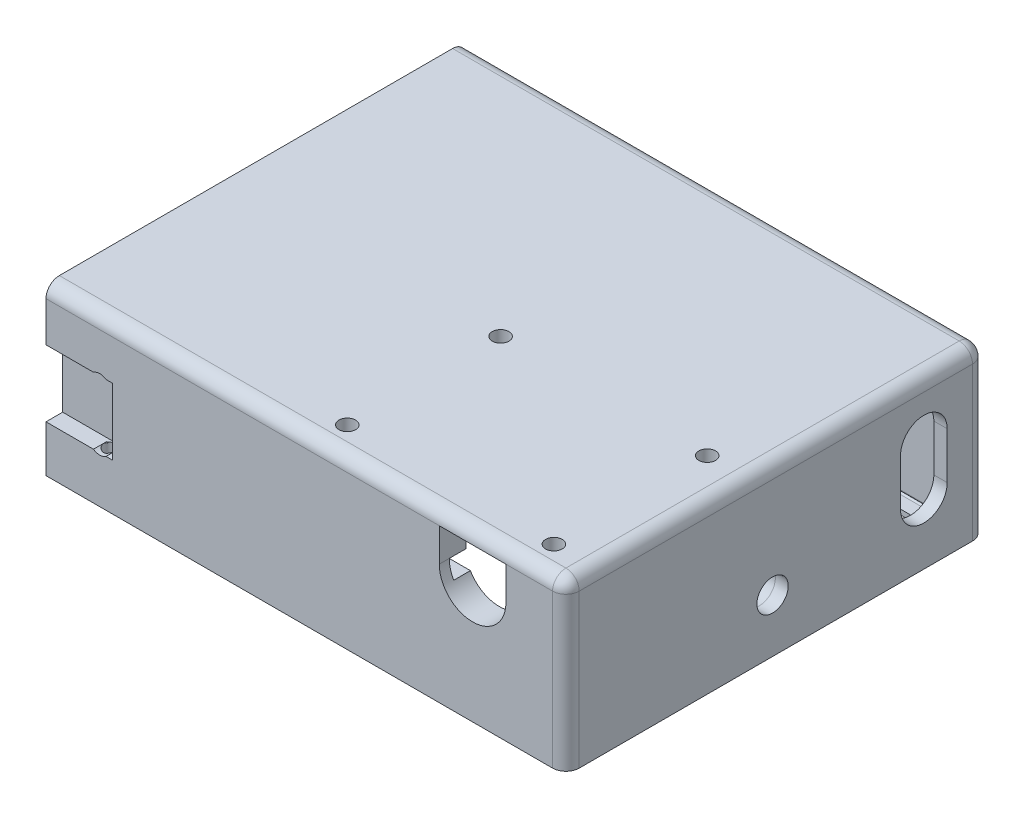
SolidWorks part; units mm, degrees
note: The reader was unsure of these and kept them because the rebuilt part matched: shared geometry of "Sketch1<4>", "Sketch18<3>".
ref_plane "Front Plane" through (0, 0, 0) normal (0, 0, 1) x (1, 0, 0)
ref_plane "Top Plane" through (0, 0, 0) normal (0, 1, 0) x (1, 0, 0)
ref_plane "Right Plane" through (0, 0, 0) normal (1, 0, 0) x (0, 0, -1)
sketch "Sketch1" plane through (0, 0, 0) normal (0, 1, 0) x (1, 0, 0)
  line L1 (0, 0) -> (80, 0)
  line L2 (0, 0) -> (0, 63)
  line L3 (0, 63) -> (80, 63)
  line L4 (80, 0) -> (80, 63)
  line L5 (2, 4) -> (78, 4)
  line L6 (2, 4) -> (2, 59)
  line L7 (2, 59) -> (78, 59)
  line L8 (78, 4) -> (78, 59)
  line L9 (0, 0) -> (2, 0)
  line L10 (0, 0) -> (0, 63)
  line L11 (0, 63) -> (2, 63)
  line L12 (2, 0) -> (2, 63)
  dimension "D1" = 63
  dimension "Length" = 80
  dimension "D2" = 2
  dimension "D3" = 4
  dimension "D4" = 2
  dimension "D5" = 4
extrude "Boss-Extrude2" add sketch "Sketch1" along normal blind 25 contours L1 L4 L3 L2
extrude "Cut-Extrude1" cut sketch "Sketch1<4>" along normal blind 23 contours L5 L8 L7 L6
sketch "Sketch1<4>" plane through (0, 0, 0) normal (0, 1, 0) x (1, 0, 0) same geometry as "Sketch1"
sketch "Sketch3" plane through (80, 0, 0) normal (1, 0, 0) x (0, 0, -1)
  line L0 (46.5, 10) -> (16.5, 10) construction
  line L1 (46.5, 7.5) -> (16.5, 7.5)
  line L2 (46.5, 12.5) -> (16.5, 12.5)
  line L3 (4, 0) -> (59, 0) construction
  line L4 (0, 25) -> (0, 0) construction
  arc A0 (46.5, 7.5) -> (46.5, 12.5) centre (46.5, 10) ccw
  arc A1 (16.5, 12.5) -> (16.5, 7.5) centre (16.5, 10) ccw
  point P2 (31.5, 10)
  dimension "D1" = 30
  dimension "D2" = 5
  dimension "D3" = 10
  dimension "D4" = 31.5
sketch "Sketch4" plane through (0, 23, 0) normal (0, -1, 0) x (1, 0, 0)
  line L0 (2, -4) -> (78, -4) construction
  line L1 (29.5, -4) -> (31.5, -4)
  line L2 (29.5, -4) -> (29.5, -59)
  line L3 (29.5, -59) -> (31.5, -59)
  line L4 (31.5, -4) -> (31.5, -59)
  line L5 (2, -59) -> (78, -59) construction
  line L6 (2, -4) -> (2, -59) construction
  dimension "D1" = 2
  dimension "D2" = 27.5
extrude "Boss-Extrude3" add sketch "Sketch4" along normal blind 10
fillet "Fillet1" radius 2 8 edges at (40, 25, -63) (0, 12.5, -63) (0, 25, -31.5) (0, 12.5, 0) (40, 25, 0) (80, 12.5, 0) (80, 25, -31.5) (80, 12.5, -63)
sketch "Sketch5" plane through (0, 0, 0) normal (0, -1, 0) x (-1, 0, 0)
  line L1 (0, 0) -> (-2, 0)
  line L2 (0, 0) -> (0, 63)
  line L3 (0, 63) -> (-2, 63)
  line L4 (-2, 0) -> (-2, 63)
extrude "Cut-Extrude3" cut sketch "Sketch5" against normal through all
sketch "Sketch6" plane through (2, 0, 0) normal (-1, 0, 0) x (0, 0, 1)
  line L0 (-4, 23) -> (-4, 0) construction
  line L1 (-4, 0.75) -> (-1.8, 0.75)
  line L2 (-4, 0.75) -> (-4, 2.95)
  line L3 (-4, 2.95) -> (-1.8, 2.95)
  line L4 (-1.8, 0.75) -> (-1.8, 2.95)
  line L5 (-59, 23) -> (-59, 0) construction
  line L6 (-59, 0.75) -> (-61.2, 0.75)
  line L7 (-59, 0.75) -> (-59, 2.95)
  line L8 (-59, 2.95) -> (-61.2, 2.95)
  line L9 (-61.2, 0.75) -> (-61.2, 2.95)
  line L10 (0, 0) -> (-63, 0) construction
  line L11 (0, 23) -> (0, 0) construction
  point P12 (-60.1, 2.95)
  point P17 (-1.8, 1.85)
  dimension "D1" = 2.2
  dimension "D2" = 2.2
  dimension "D3" = 2.2
  dimension "D4" = 0.75
  dimension "D5" = 0.75
  dimension "1.5" = 2.2
  dimension "D6" = 1.8
extrude "Cut-Extrude4" cut sketch "Sketch6" against normal blind 76 contours L6 L9 L8 L7 | L1 L4 L3 L2
sketch "Sketch7" plane through (0, 0, -63) normal (0, 0, -1) x (-1, 0, 0)
  line L0 (-2, 0) -> (-2, 23) construction
  line L1 (-2, 7) -> (-12, 7)
  line L2 (-2, 7) -> (-2, 17)
  line L3 (-2, 17) -> (-12, 17)
  line L4 (-12, 7) -> (-12, 17)
  line L5 (-78, 25) -> (-2, 25) construction
  dimension "D1" = 10
  dimension "D2" = 8
  dimension "D3" = 10
extrude "Cut-Extrude5" cut sketch "Sketch7" against normal blind 2.5
sketch "Sketch8" plane through (0, 7, 0) normal (0, 1, 0) x (1, 0, 0)
  line L0 (12, 60.5) -> (12, 63) construction
  line L1 (12, 60.5) -> (2, 60.5) construction
  circle A0 centre (10, 61.5) radius 0.875
  dimension "D1" = 1.75
  dimension "D2" = 2
  dimension "D3" = 1
extrude "Cut-Extrude6" cut sketch "Sketch8" against normal blind 1.5 and the other way blind 11.5
sketch "Sketch9" plane through (0, 0, 0) normal (0, 0, 1) x (1, 0, 0)
  line L0 (2, 23) -> (2, 0) construction
  line L1 (2, 7) -> (12, 7)
  line L2 (2, 7) -> (2, 17)
  line L3 (2, 17) -> (12, 17)
  line L4 (12, 7) -> (12, 17)
  line L5 (2, 25) -> (78, 25) construction
  dimension "D1" = 10
  dimension "D2" = 10
  dimension "D3" = 8
extrude "Cut-Extrude7" cut sketch "Sketch9" against normal blind 2.5
sketch "Sketch10" plane through (0, 7, 0) normal (0, 1, 0) x (1, 0, 0)
  line L0 (12, 2.5) -> (12, 0) construction
  line L1 (2, 2.5) -> (12, 2.5) construction
  circle A0 centre (10, 1.5) radius 0.875
  dimension "D1" = 1.75
  dimension "D2" = 2
  dimension "D3" = 1
extrude "Cut-Extrude8" cut sketch "Sketch10" against normal blind 1.5 and the other way blind 11.5
sketch "Sketch11" plane through (0, 0, -63) normal (0, 0, -1) x (-1, 0, 0)
  line L0 (-12, 7) -> (-2, 7) construction
  line L1 (-9.123, 7) -> (-10.8, 7)
  line L2 (-12, 12) -> (-17.0656, 12) construction
  line L3 (-12, 17) -> (-12, 7) construction
  line L4 (-9.123, 17) -> (-10.8, 17)
  spline S0 degree 2 poles (-10.8, 7) (-9.9802, 6.3956) (-9.123, 7) knots 0 0 0 1 1 1
  spline S1 degree 2 poles (-10.8, 17) (-9.9802, 17.6044) (-9.123, 17) knots 0 0 0 1 1 1
  dimension "D1" = 0.3
  dimension "D2" = 1.2
extrude "Cut-Extrude9" cut sketch "Sketch11" against normal blind 2 contours S0 L1 | S1 L4
sketch "Sketch12" plane through (0, 0, 0) normal (0, 0, 1) x (1, 0, 0)
  line L0 (2, 7) -> (12, 7) construction
  line L2 (11, 7) -> (9.1201, 7)
  line L3 (12, 12) -> (18.6065, 12) construction
  line L4 (12, 7) -> (12, 17) construction
  line L5 (11, 17) -> (9.1201, 17)
  spline S0 degree 2 poles (11, 7) (10.0566, 6.3998) (9.1201, 7) knots 0 0 0 1 1 1
  spline S1 degree 2 poles (11, 17) (10.0566, 17.6002) (9.1201, 17) knots 0 0 0 1 1 1
  dimension "D1" = 0.3
  dimension "D2" = 1
extrude "Cut-Extrude10" cut sketch "Sketch12" against normal blind 2 contours S0 L2 | S1 L5
sketch "Sketch13" plane through (0, 23, 0) normal (0, -1, 0) x (-1, 0, 0)
  line L0 (-78, 4) -> (-78, 59) construction
  line L1 (-2, 4) -> (-78, 4) construction
  line L2 (-78, 2) -> (-78, 61) construction
  line L4 (-78, 61) -> (-2, 61) construction
  circle A0 centre (-32.38, 56.23) radius 0.6
  circle A1 centre (-32.38, 41) radius 0.6
  circle A2 centre (-73, 41) radius 0.6
  circle A3 centre (-73, 56.23) radius 0.6
  dimension "D1" = 1.2
  dimension "D2" = 1.2
  dimension "D3" = 1.2
  dimension "D4" = 1.2
  dimension "D5" = 15.23
  dimension "D6" = 15.23
  dimension "D7" = 40.62
  dimension "D8" = 5
  dimension "D9" = 37
  dimension "D10" = 5
  dimension "D11" = 40.62
  dimension "D12" = 4.77
fillet "Fillet2" radius 0.3 12 edges at (40, 2.95, -4) (40, 2.95, -1.8) (2, 1.85, -1.8) (2, 2.95, -2.9) (40, 2.95, -59) (40, 0.75, -61.2) (40, 2.95, -61.2) (2, 2.95, -60.1) (2, 0.75, -60.1) (2, 1.85, -61.2) (2, 0.75, -2.9) (40, 0.75, -1.8)
sketch "Sketch15" plane through (29.5, 0, 0) normal (-1, 0, 0) x (0, 0, 1)
  line L0 (-4, 23) -> (-59, 23) construction
  line L1 (-4, 13) -> (-9, 13)
  line L2 (-4, 13) -> (-4, 23)
  line L3 (-4, 23) -> (-9, 23)
  line L4 (-9, 13) -> (-9, 23)
  dimension "D1" = 5
extrude "Cut-Extrude13" cut sketch "Sketch15" against normal up to next
fillet "Fillet3" radius 1 5 edges at (31.5, 18, -59) (29.5, 18, -59) (31.5, 13, -34) (29.5, 13, -34) (30.5, 13, -9)
sketch "Sketch17" plane through (0, 0, 0) normal (0, 0, 1) x (1, 0, 0)
  line L0 (78, 23) -> (2, 23) construction
  line L3 (78, 0) -> (78, 23) construction
  circle A2 centre (66, 18) radius 5
  dimension "D1" = 10
  dimension "D2" = 5
  dimension "D3" = 12
sketch "Sketch18" plane through (80, 0, 0) normal (1, 0, 0) x (0, 0, -1)
  line L0 (53.7, 16.5) -> (53.7, 9.5) construction
  line L1 (57.2, 16.5) -> (57.2, 9.5)
  line L2 (50.2, 16.5) -> (50.2, 9.5)
  line L3 (61, 0) -> (61, 23) construction
  line L5 (4, 0) -> (59, 0) construction
  line L6 (59, 23) -> (59, 3.25) construction
  line L7 (61, 23) -> (2, 23) construction
  arc A0 (57.2, 16.5) -> (50.2, 16.5) centre (53.7, 16.5) ccw
  arc A1 (50.2, 9.5) -> (57.2, 9.5) centre (53.7, 9.5) ccw
  circle A2 centre (31, 8) radius 2.35
  point P2 (53.7, 13)
  dimension "D5" = 4.7
  dimension "D1" = 7
  dimension "D2" = 7
  dimension "D3" = 1.8
  dimension "D4" = 10
  dimension "D6" = 8
  dimension "D7" = 30
extrude "Cut-Extrude16" cut sketch "Sketch18" against normal blind 15 draft 2 contours A2 draft outward yes
sketch "Sketch19" plane through (0, 23, 0) normal (0, -1, 0) x (1, 0, 0)
  line L0 (2, -4) -> (78, -4) construction
  line L1 (78, -4) -> (78, -59) construction
  line L2 (78, -4) -> (78, -59) construction
  circle A0 centre (74, -4.2) radius 1.25
  circle A1 centre (74, -27.2) radius 1.25
  circle A2 centre (43, -27.2) radius 1.25
  circle A3 centre (43, -4.2) radius 1.25
  dimension "D4" = 2.5
  dimension "D5" = 2.5
  dimension "D6" = 2.5
  dimension "D7" = 2.5
  dimension "D1" = 31
  dimension "D2" = 23
  dimension "D3" = 0.2
  dimension "D8" = 23
  dimension "D9" = 31
  dimension "D10" = 4
  dimension "D12" = 0.2
extrude "Cut-Extrude17" cut sketch "Sketch19" against normal blind 10
extrude "Cut-Extrude18" cut sketch "Sketch17" against normal up to next
sketch "Sketch20" plane through (78, 0, 0) normal (-1, 0, 0) x (0, 0, 1)
  circle A0 centre (-31, 8) radius 3.5
  circle M5 centre (-31, 8) radius 2.4198
  dimension "D1" = 7
extrude "Boss-Extrude4" add sketch "Sketch20" along normal blind 5 contours A0 M5
sketch "Sketch21" plane through (0, 0, -59) normal (0, 0, 1) x (1, 0, 0)
  line L0 (78, 23) -> (78, 3.25) construction
  line L1 (32.5, 23) -> (78, 23) construction
  circle A0 centre (76.7, 20.5) radius 0.75
  circle A1 centre (76.7, 5.5) radius 0.75
  circle A2 centre (36.2, 5.5) radius 0.75
  circle A3 centre (36.2, 20.5) radius 0.75
  dimension "D1" = 1.3
  dimension "D9" = 1.5
  dimension "D10" = 1.5
  dimension "D11" = 1.5
  dimension "D12" = 1.5
  dimension "D2" = 2.5
  dimension "D3" = 15
  dimension "D4" = 40.5
  dimension "D5" = 15
  dimension "D6" = 1.3
  dimension "D7" = 40.5
  dimension "D8" = 2.5
extrude "Cut-Extrude19" cut sketch "Sketch21" against normal blind 10
sketch "Sketch22" plane through (0, 0, -4) normal (0, 0, -1) x (-1, 0, 0)
  line L0 (-78, 23) -> (-78, 3.25) construction
  line L1 (-78, 15.5) -> (-40, 15.5)
  line L2 (-78, 15.5) -> (-78, 18)
  line L3 (-78, 18) -> (-40, 18)
  line L4 (-40, 15.5) -> (-40, 18)
  line L5 (-2, 23) -> (-41.7661, 23) construction
  dimension "D1" = 2.5
  dimension "D2" = 5
  dimension "D3" = 38
extrude "Cut-Extrude20" cut sketch "Sketch22" against normal blind 2.5 contours L1 L4 L3 L2
sketch "Sketch23" plane through (0, 0, 0) normal (0, 0, 1) x (1, 0, 0)
  line L0 (78, 23) -> (66, 23) construction
  line L1 (71, 23) -> (61, 23)
  line L2 (71, 23) -> (71, 18)
  line L3 (71, 18) -> (61, 18)
  line L4 (61, 23) -> (61, 18)
  line L5 (71, 23) -> (61, 18) construction
  line L6 (71, 18) -> (61, 23) construction
  line L7 (78, 0) -> (78, 23) construction
  circle A0 centre (66, 18) radius 5 construction
  point P4 (66, 20.5)
  dimension "D1" = 7
extrude "Cut-Extrude21" cut sketch "Sketch23" against normal blind 10
sketch "Sketch24" plane through (0, 0, -4) normal (0, 0, -1) x (-1, 0, 0)
  line L1 (-46, 13) -> (-58, 13)
  line L2 (-46, 13) -> (-46, 20)
  line L3 (-46, 20) -> (-58, 20)
  line L4 (-58, 13) -> (-58, 20)
  line L5 (-46, 13) -> (-58, 20) construction
  line L6 (-46, 20) -> (-58, 13) construction
  line L7 (-44.2339, 23) -> (-61, 23) construction
  line L8 (-40, 15.5) -> (-40, 18) construction
  point P4 (-52, 16.5)
  dimension "D1" = 7
  dimension "D2" = 3
  dimension "D3" = 12
  dimension "D4" = 6
extrude "Cut-Extrude22" cut sketch "Sketch24" against normal blind 2
extrude "Cut-Extrude23" cut sketch "Sketch18<3>" against normal blind 2 contours L2 A1 L1 A0
sketch "Sketch18<3>" plane through (80, 0, 0) normal (1, 0, 0) x (0, 0, -1) same geometry as "Sketch18"
equation "\"D10@Sketch13\"=\"D8@Sketch13\""
equation "\"D11@Sketch13\"=\"D7@Sketch13\""
equation "\"D3@Sketch13\"=\"D4@Sketch13\""
equation "\"D2@Sketch13\"=\"D4@Sketch13\""
equation "\"D1@Sketch13\"=\"D4@Sketch13\""
equation "\"D5@Sketch19\"=\"D4@Sketch19\""
equation "\"D6@Sketch19\"=\"D4@Sketch19\""
equation "\"D7@Sketch19\"=\"D4@Sketch19\""
equation "\"D9@Sketch19\"=\"D1@Sketch19\""
